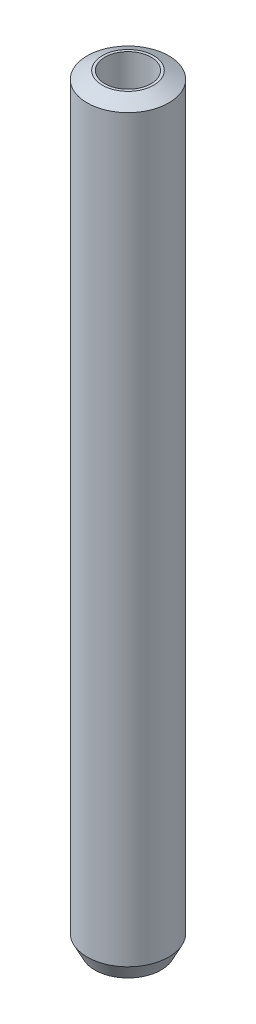
SolidWorks part; units mm, degrees
ref_plane "Front Plane" through (0, 0, 0) normal (0, 0, 1) x (1, 0, 0)
ref_plane "Top Plane" through (0, 0, 0) normal (0, 1, 0) x (1, 0, 0)
ref_plane "Right Plane" through (0, 0, 0) normal (1, 0, 0) x (0, 0, -1)
sketch "Sketch1" plane through (0, 0, 0) normal (0, 1, 0) x (1, 0, 0)
  circle A0 centre (0, 0) radius 15
  dimension "SHAFT_OD" = 30
extrude "Boss-Extrude1" add sketch "Sketch1" along normal blind 280.1338
sketch "Sketch2" plane through (0, 0, 0) normal (0, 1, 0) x (1, 0, 0)
  circle A0 centre (0, 0) radius 8.4756
  dimension "BORE_D" = 16.9511
extrude "Cut-Extrude1" cut sketch "Sketch2" along normal through all
chamfer "Chamfer1" distance 2.8328 angle 63.033 2 edges at (0, 280.1338, 15) (0, 0, 15) first distance on face at (0, 280.1338, 15) first distance on face at (0, 0, 8.4756)
